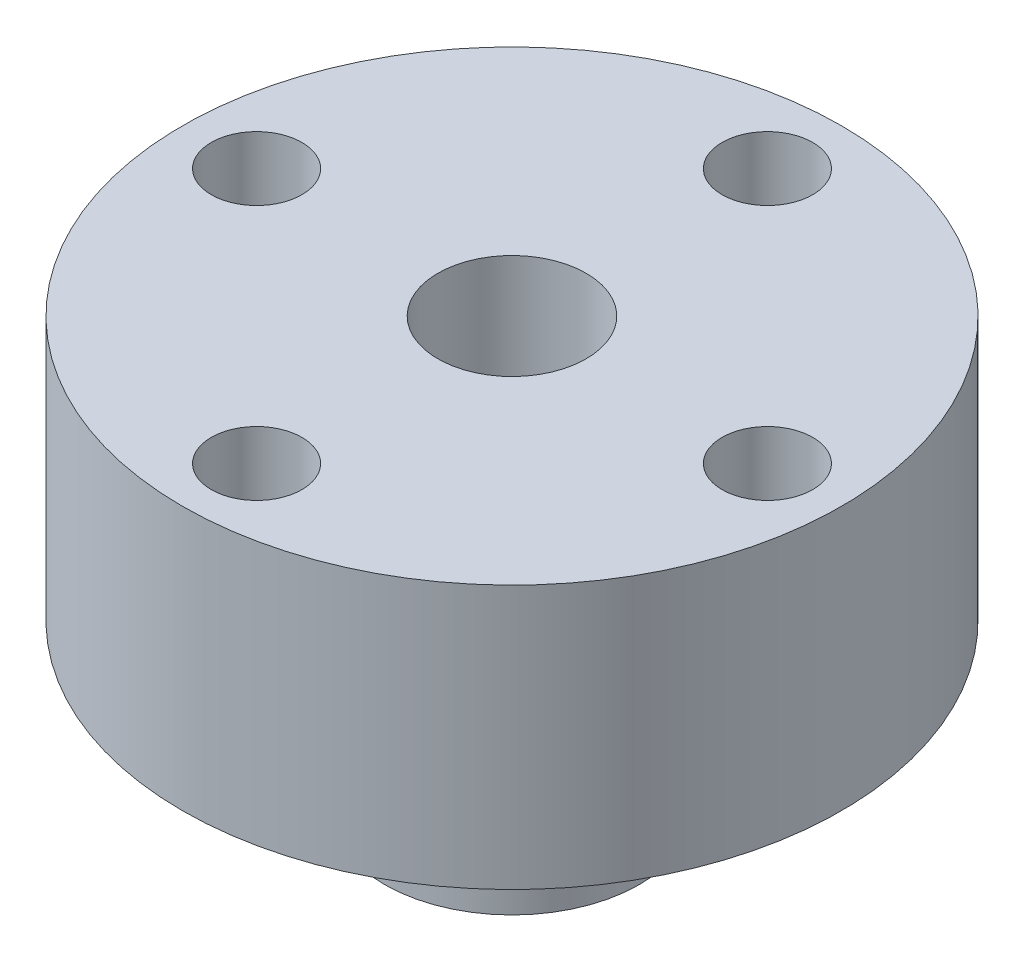
SolidWorks part; units mm, degrees
ref_plane "Front Plane" through (0, 0, 0) normal (0, 0, 1) x (1, 0, 0)
ref_plane "Top Plane" through (0, 0, 0) normal (0, 1, 0) x (1, 0, 0)
ref_plane "Right Plane" through (0, 0, 0) normal (1, 0, 0) x (0, 0, -1)
sketch "Sketch1" plane through (0, 0, 0) normal (0, 1, 0) x (1, 0, 0)
  circle A0 centre (0, 0) radius 3.875
  dimension "D1" = 7.75
extrude "Boss-Extrude1" add sketch "Sketch1" along normal blind 9 and the other way blind 4
sketch "Sketch2" plane through (0, 0, 0) normal (0, 1, 0) x (1, 0, 0)
  circle A0 centre (0, 0) radius 5.4
  dimension "D1" = 10.8
extrude "Boss-Extrude2" add sketch "Sketch2" along normal up to surface (9 mm away) up to face at (0, 9, 3.875)
sketch "Sketch7" plane through (0, 9, 0) normal (0, 1, 0) x (1, 0, 0)
  circle A0 centre (0, 0) radius 10
  dimension "D1" = 20
extrude "Boss-Extrude4" add sketch "Sketch7" against normal blind 8
sketch "Sketch8" plane through (0, -4, 0) normal (0, -1, 0) x (1, 0, 0)
  circle A0 centre (0, 0) radius 2.25
  dimension "D1" = 4.5
extrude "Cut-Extrude4" cut sketch "Sketch8" against normal through all both and the other way through all
sketch "Sketch3" plane through (0, 9, 0) normal (0, 1, 0) x (1, 0, 0)
  circle A0 centre (0, 0) radius 7.75 construction
  circle A1 centre (-7.75, 0) radius 1.375
  dimension "D1" = 15.5
  dimension "D2" = 2.75
extrude "Cut-Extrude2" cut sketch "Sketch3" against normal up to surface (9 mm away) and the other way through all up to face at (0, 0, 3.875)
pattern_circular "CirPattern2" count 4 over 360 about axis through (0, 1, 0) along (0, 1, 0) of "Cut-Extrude2"
